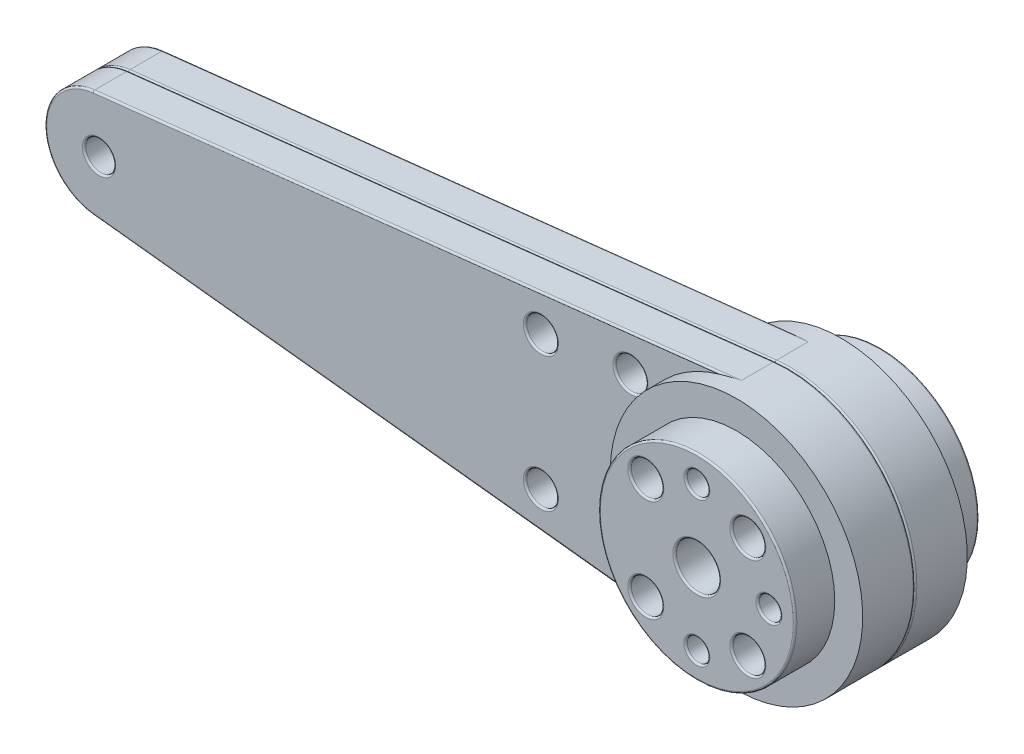
SolidWorks part; units mm, degrees
ref_plane "정면" through (0, 0, 0) normal (0, 0, 1) x (1, 0, 0)
ref_plane "윗면" through (0, 0, 0) normal (0, 1, 0) x (1, 0, 0)
ref_plane "우측면" through (0, 0, 0) normal (1, 0, 0) x (0, 0, -1)
sketch "스케치1" plane through (0, 0, 0) normal (0, 0, 1) x (1, 0, 0)
  line L0 (0, 0) -> (5.6569, 5.6569) construction
  line L1 (0, 0) -> (9.1372, 0) construction
  line L2 (0, 0) -> (-72.59, 0) construction
  line L3 (-73.2512, 5.9635) -> (-1.5429, 13.9147)
  line L4 (-73.2512, -5.9635) -> (-1.5429, -13.9147)
  line L5 (-27.59, 11.0265) -> (-27.59, -11.0265) construction
  line L6 (-9.6569, 13.015) -> (-9.6569, -13.015) construction
  arc A0 (-1.5429, -13.9147) -> (-1.5429, 13.9147) centre (0, 0) ccw
  circle A1 centre (5.6569, 5.6569) radius 1.8
  circle A2 centre (5.6569, -5.6569) radius 1.8
  circle A3 centre (-5.6569, -5.6569) radius 1.8
  circle A4 centre (-5.6569, 5.6569) radius 1.8
  circle A5 centre (0, 0) radius 4
  arc A6 (-73.2512, 5.9635) -> (-73.2512, -5.9635) centre (-72.59, 0) ccw
  circle A7 centre (-72.59, 0) radius 1.65
  circle A8 centre (0, 0) radius 10.9
  circle A10 centre (-23.59, 7.4455) radius 1.75
  circle A12 centre (-13.6569, 8.547) radius 1.75
  circle A13 centre (-13.6569, -8.547) radius 1.75
  circle A14 centre (-23.59, -7.4455) radius 1.75
  point P15 (0, 0)
  dimension "D1" = 28
  dimension "D3" = 3.6
  dimension "D6" = 8
  dimension "D8" = 12
  dimension "D9" = 3.3
  dimension "D10" = 21.8
  dimension "D13" = 3.5
  dimension "D14" = 3.5
  dimension "D2" = 45
  dimension "D4" = 8
  dimension "D7" = 72.59
  dimension "D11" = 45
  dimension "D12" = 4
  dimension "D15" = 4
  dimension "D16" = 4
  dimension "D17" = 4
  dimension "D18" = 4
  dimension "D5" = 4
extrude "보스-돌출1" add sketch "스케치1" along normal blind 3.9 contours L3 A6 L4 L5 A7 | L4 A0 L3 L5 A8 | A8 A1 A2 A3 A4 A5 | A5 region at (-33.4793, 0, 0) region at (0, 0, 0) region at (-10.5917, 0, 0)
extrude "보스-돌출2" add sketch "스케치1<6>" against normal blind 6.3 contours A8 A1 A2 A3 A4 A5 | A5 region at (0, 0, 0) region at (-10.5917, 0, 0)
sketch "스케치1<6>" plane through (0, 0, 0) normal (0, 0, 1) x (1, 0, 0) same geometry as "스케치1"
sketch "스케치2" plane through (0, 0, 3.9) normal (0, 0, 1) x (1, 0, 0)
  line L0 (-27.59, 11.0265) -> (-27.59, -11.0265) construction
  line L1 (0, 0) -> (-38.7117, 0) construction
  line L2 (-1.5429, 13.9147) -> (-73.2512, 5.9635)
  line L3 (-73.2512, -5.9635) -> (-1.5429, -13.9147)
  line L4 (-1.5429, 13.9147) -> (-73.2512, 5.9635)
  line L5 (-73.2512, -5.9635) -> (-1.5429, -13.9147)
  line L7 (-12, 12.7552) -> (-12, -12.7552) construction
  line L8 (-12, 12.7552) -> (-8.834, 4.4463) construction
  line L9 (-12, -12.7552) -> (-8.834, -4.4463) construction
  arc A2 (-73.2512, 5.9635) -> (-73.2512, -5.9635) centre (-72.59, 0) ccw
  arc A3 (-1.5429, -13.9147) -> (-1.5429, 13.9147) centre (0, 0) ccw
  arc A4 (-73.2512, 5.9635) -> (-73.2512, -5.9635) centre (-72.59, 0) ccw
  arc A5 (-1.5429, -13.9147) -> (-1.5429, 13.9147) centre (0, 0) ccw
  circle A7 centre (-5.6569, 5.6569) radius 3.4
  circle A8 centre (-5.6569, -5.6569) radius 3.4
  circle A9 centre (-7.75, 0) radius 2.6317
  circle A10 centre (-7.75, 0) radius 1.65
  circle A13 centre (5.6569, 5.6569) radius 3.4
  circle A14 centre (5.6569, -5.6569) radius 3.4
  circle A15 centre (0, 7.75) radius 2.6317
  circle A16 centre (7.75, 0) radius 2.6317
  circle A17 centre (0, -7.75) radius 2.6317
  circle A18 centre (0, 7.75) radius 1.65
  circle A19 centre (7.75, 0) radius 1.65
  circle A20 centre (0, -7.75) radius 1.65
  dimension "D6" = 6.8
  dimension "D7" = 3.3
  dimension "D2" = 45
  dimension "D8" = 7.75
  dimension "D9" = 12
  dimension "D12" = 7.75
  dimension "D13" = 7.75
  dimension "D14" = 7.75
  dimension "D1" = 0
sketch "스케치3" plane through (0, 0, 0) normal (0, 0, -1) x (-1, 0, 0)
  circle A0 centre (0, 0) radius 14
  circle A1 centre (0, 0) radius 10.9 construction
  circle A2 centre (0, 0) radius 10.9
  circle M5 centre (0, 0) radius 10.9
  arc M8 (1.5429, 13.9147) -> (1.5429, -13.9147) centre (0, 0) ccw
  dimension "D1" = 28
extrude "보스-돌출3" add sketch "스케치3" along normal blind 1.9 contours A0 M8 M5 region at (-10.1357, -9.074, 0)
sketch "스케치4" plane through (0, 0, -6.3) normal (0, 0, -1) x (-1, 0, 0)
  circle A0 centre (0, 0) radius 2.45
  dimension "D1" = 4.9
extrude "컷-돌출2" cut sketch "스케치4" against normal through all
sketch "스케치5" plane through (0, 0, 3.9) normal (0, 0, 1) x (1, 0, 0)
  line L0 (0, 14) -> (0, -14) construction
  line L1 (0, 0) -> (9.1372, 0) construction
  arc A0 (-1.5429, -13.9147) -> (-1.5429, 13.9147) centre (0, 0) ccw construction
  circle A2 centre (0, 8) radius 1.25
  circle A4 centre (0, -8) radius 1.25
  circle A6 centre (8, 0) radius 1.25
  dimension "D2" = 2.5
  dimension "D5" = 2.5
  dimension "D8" = 2.5
  dimension "D3" = 8
  dimension "D6" = 8
  dimension "D9" = 8
extrude "컷-돌출3" cut sketch "스케치5" against normal through all contours A2 | A6 | A4
fillet "필렛2" radius 0.2 26 edges at (10.9, 0, -6.3) (7.4569, 5.6569, -6.3) (7.4569, -5.6569, -6.3) (-3.8569, -5.6569, -6.3) (-3.8569, 5.6569, -6.3) (-2.45, 0, -6.3) (1.25, -8, -6.3) (9.25, 0, -6.3) (1.25, 8, -6.3) (7.4569, 5.6569, 3.9) (7.4569, -5.6569, 3.9) (-3.8569, -5.6569, 3.9) (-3.8569, 5.6569, 3.9) (-21.84, -7.4455, 3.9) (14, 0, 3.9) (-37.3971, -9.9391, 3.9) (-78.59, 0, 3.9) (-37.3971, 9.9391, 3.9) (-70.94, 0, 3.9) (-21.84, 7.4455, 3.9) (-11.9069, 8.547, 3.9) (-11.9069, -8.547, 3.9) (-2.45, 0, 3.9) (1.25, -8, 3.9) (9.25, 0, 3.9) (1.25, 8, 3.9)
fillet "필렛3" radius 0.2 8 edges at (-37.3971, -9.9391, 0) (-78.59, 0, 0) (-70.94, 0, 0) (-37.3971, 9.9391, 0) (-11.9069, 8.547, 0) (-21.84, 7.4455, 0) (-11.9069, -8.547, 0) (-21.84, -7.4455, 0)
mirror "대칭 복사1" about plane through (0, 0, 3.9) normal (0, 0, 1) of bodies 113
